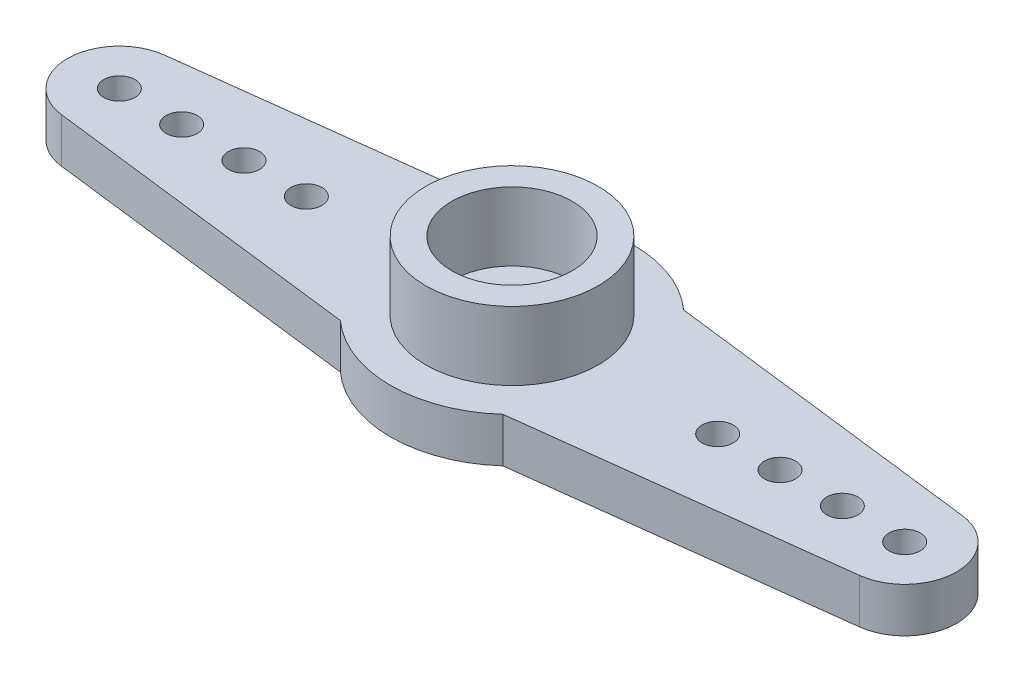
SolidWorks part; units mm, degrees
ref_plane "Front Plane" through (0, 0, 0) normal (0, 0, 1) x (1, 0, 0)
ref_plane "Top Plane" through (0, 0, 0) normal (0, 1, 0) x (1, 0, 0)
ref_plane "Right Plane" through (0, 0, 0) normal (1, 0, 0) x (0, 0, -1)
sketch "Sketch1" plane through (0, 0, 0) normal (0, 1, 0) x (1, 0, 0)
  line L0 (0, 18.3078) -> (0, -20.904) construction
  line L1 (-19.2032, 2.4815) -> (-3.9115, 4.35)
  line L2 (-19.2032, -2.4815) -> (-3.9115, -4.35)
  line L3 (-18.9, 0) -> (0, 0) construction
  line L4 (19.2032, -2.4815) -> (3.9115, -4.35)
  line L5 (19.2032, 2.4815) -> (3.9115, 4.35)
  circle A0 centre (0, 0) radius 5.85
  circle A1 centre (0, 0) radius 1.25
  arc A2 (-19.2032, -2.4815) -> (-19.2032, 2.4815) centre (-18.9, 0) cw
  circle A3 centre (-18.9, 0) radius 0.75
  circle A4 centre (-15.9, 0) radius 0.75
  circle A5 centre (-12.9, 0) radius 0.75
  circle A6 centre (-9.9, 0) radius 0.75
  circle A7 centre (9.9, 0) radius 0.75
  circle A8 centre (12.9, 0) radius 0.75
  circle A9 centre (15.9, 0) radius 0.75
  circle A10 centre (18.9, 0) radius 0.75
  arc A11 (19.2032, -2.4815) -> (19.2032, 2.4815) centre (18.9, 0) ccw
  point P9 (0, 0)
  point P19 (0, 0)
  dimension "D1" = 2.5
  dimension "D2" = 1.5
  dimension "D3" = 1.5
  dimension "D4" = 1.5
  dimension "D5" = 1.5
  dimension "D9" = 11.7
  dimension "D11" = 37.8
  dimension "D12" = 2.5
  dimension "D6" = 3
  dimension "D7" = 3
  dimension "D8" = 3
  dimension "D10" = 8.7
extrude "Boss-Extrude1" add sketch "Sketch1" along normal blind 2.15 contours A0 A1 | A2 L2 A0 L1 A6 A5 A4 A3 | L4 A11 L5 A0 A10 A8 A7 A9 region at (-11.5337, 0, -3.2219) region at (0, 0, -5.6845) region at (11.5337, 0, -3.2219)
sketch "Sketch2" plane through (0, 2.15, 0) normal (0, 1, 0) x (1, 0, 0)
  circle A0 centre (0, 0) radius 2.9
  circle A1 centre (0, 0) radius 4.15
  dimension "D1" = 8.3
  dimension "D2" = 5.8
extrude "Boss-Extrude2" add sketch "Sketch2" along normal blind 3.3
